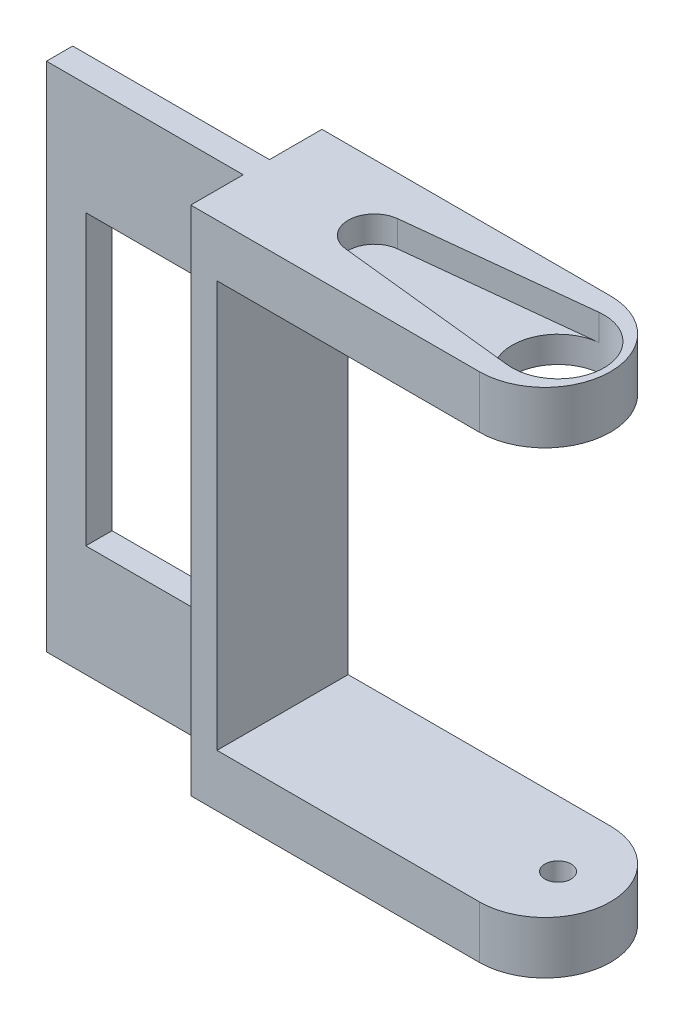
SolidWorks part; units mm, degrees
ref_plane "Front Plane" through (0, 0, 0) normal (0, 0, 1) x (1, 0, 0)
ref_plane "Top Plane" through (0, 0, 0) normal (0, 1, 0) x (1, 0, 0)
ref_plane "Right Plane" through (0, 0, 0) normal (1, 0, 0) x (0, 0, -1)
sketch "Sketch1" plane through (0, 0, 0) normal (0, 0, 1) x (1, 0, 0)
  line L0 (-27, 17.3437) -> (0, 17.3437)
  line L1 (0, 17.3437) -> (0, 13.3437)
  line L2 (0, 13.3437) -> (-25, 13.3437)
  line L3 (-25, 13.3437) -> (-25, -17.6563)
  line L4 (-25, -17.6563) -> (0, -17.6563)
  line L5 (0, -17.6563) -> (0, -21.6563)
  line L6 (0, -21.6563) -> (-27, -21.6563)
  line L7 (-27, -21.6563) -> (-27, 17.3437)
  dimension "D1" = 25
  dimension "D2" = 31
  dimension "D3" = 4
  dimension "D4" = 4
  dimension "D5" = 2
extrude "Boss-Extrude1" add sketch "Sketch1" along normal blind 10
sketch "Sketch2" plane through (0, 17.3437, 0) normal (0, 1, 0) x (1, 0, 0)
  line L3 (-27, -10) -> (-27, 0) construction
  line L6 (-27, -4) -> (-27, -6)
  line L7 (-27, -6) -> (-42, -6)
  line L16 (-27, -4) -> (-42, -4)
  line L17 (-42, -4) -> (-42, -6)
  dimension "D5" = 2
  dimension "D6" = 15
extrude "Boss-Extrude2" add sketch "Sketch2" against normal blind 39
fillet "Fillet1" 2 edges at (0, 15.3437, 10) (0, 15.3437, 0) type full round first side face at (-13, -2.1563, 10) second side face at (-13, -2.1563, 0) middle face at (0, 15.3437, 5)
fillet "Fillet2" 2 edges at (0, -19.6563, 10) (0, -19.6563, 0) type full round first side face at (-14.25, -2.1563, 10) second side face at (-14.25, -2.1563, 0) middle face at (0, -19.6563, 5)
sketch "Sketch6" plane through (0, 17.3437, 0) normal (0, 1, 0) x (1, 0, 0)
  circle A0 centre (-4, -5) radius 1
  dimension "D1" = 2
extrude "Cut-Extrude3" cut sketch "Sketch6" against normal blind 43
sketch "Sketch8" plane through (0, 17.3437, 0) normal (0, 1, 0) x (1, 0, 0)
  line L0 (-18.2143, -3.0115) -> (-4.375, -1.5201)
  line L1 (-18.2143, -6.9885) -> (-4.375, -8.4799)
  arc A0 (-4.375, -1.5201) -> (-4.375, -8.4799) centre (-4, -5) cw
  arc A1 (-18.2143, -3.0115) -> (-18.2143, -6.9885) centre (-18, -5) ccw
extrude "Cut-Extrude4" cut sketch "Sketch8" against normal blind 2
sketch "Sketch9" plane through (0, 17.3437, 0) normal (0, 1, 0) x (1, 0, 0)
  circle A1 centre (-4, -5) radius 3.5
extrude "Cut-Extrude5" cut sketch "Sketch9" against normal blind 8
sketch "Sketch10" plane through (0, 0, 6) normal (0, 0, 1) x (1, 0, 0)
  line L2 (-27, 17.3437) -> (-27, -21.6563) construction
  line L3 (-27, -13.1563) -> (-27, 8.8437)
  line L4 (-27, 8.8437) -> (-39, 8.8437)
  line L5 (-27, -13.1563) -> (-39, -13.1563)
  line L6 (-39, 8.8437) -> (-39, -13.1563)
  dimension "D1" = 12
extrude "Cut-Extrude6" cut sketch "Sketch10" against normal blind 5
